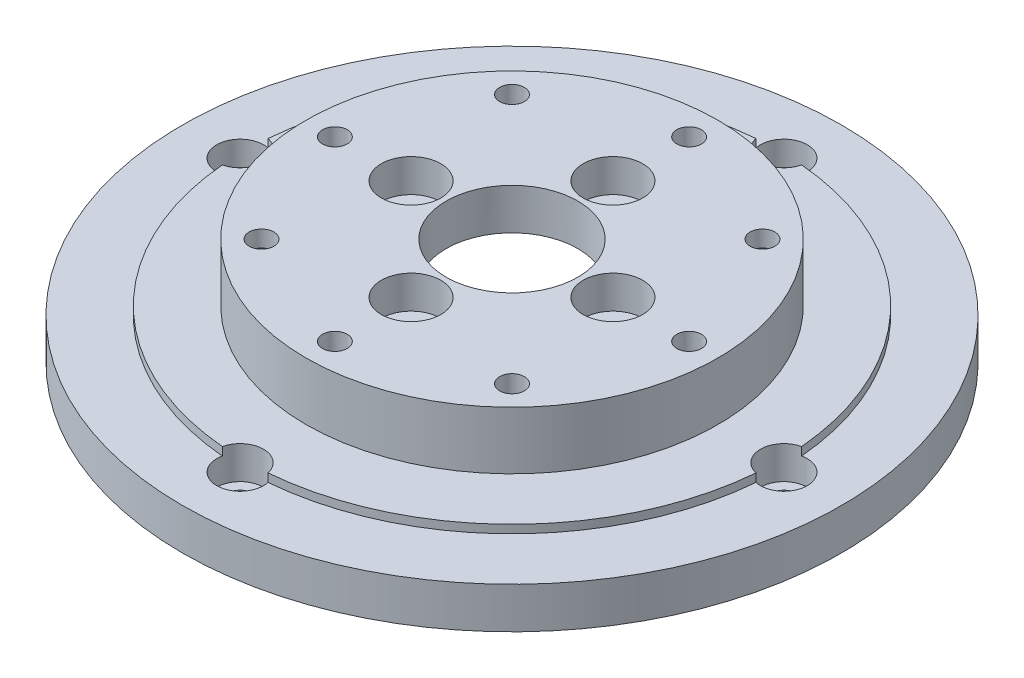
SolidWorks part; units mm, degrees
ref_plane "Front Plane" through (0, 0, 0) normal (0, 0, 1) x (1, 0, 0)
ref_plane "Top Plane" through (0, 0, 0) normal (0, 1, 0) x (1, 0, 0)
ref_plane "Right Plane" through (0, 0, 0) normal (1, 0, 0) x (0, 0, -1)
sketch "Sketch1" plane through (0, 0, 0) normal (0, 1, 0) x (1, 0, 0)
  circle A0 centre (0, 0) radius 40
  circle A2 centre (0, 0) radius 33 construction
  circle A13 centre (0, 0) radius 27.5 construction
  circle A19 centre (0.001, 0.001) radius 27.5 construction
  circle A25 centre (0.002, 0) radius 27.5 construction
  circle A31 centre (0.001, -0.001) radius 27.5 construction
  point P14 (0, 0)
  point P25 (0, 0)
  point P64 (0.001, 0)
  dimension "D1" = 80
  dimension "D3" = 66
  dimension "D6" = 55
  dimension "D10" = 4
extrude "Boss-Extrude1" add sketch "Sketch1" along normal blind 5
sketch "Sketch4" plane through (0, 5, 0) normal (0, 1, 0) x (1, 0, 0)
  circle A0 centre (0, 0) radius 32.5
  dimension "D1" = 65
extrude "Boss-Extrude2" add sketch "Sketch4" along normal blind 1
sketch "Sketch5" plane through (0, 6, 0) normal (0, 1, 0) x (1, 0, 0)
  circle A0 centre (0, 0) radius 25
  dimension "D1" = 50
extrude "Boss-Extrude3" add sketch "Sketch5" along normal blind 7
sketch "Sketch6" plane through (0, 13, 0) normal (0, 1, 0) x (1, 0, 0)
  circle A0 centre (0, 0) radius 12.25 construction
  circle A1 centre (12.25, 0) radius 2
  circle A2 centre (0, -12.25) radius 2
  circle A3 centre (-12.25, 0) radius 2
  circle A4 centre (0, 12.25) radius 2
  circle A5 centre (0, 0) radius 8
  point P14 (0, 0)
  dimension "D1" = 24.5
  dimension "D2" = 4
  dimension "D4" = 16
  dimension "D3" = 4
extrude "Cut-Extrude1" cut sketch "Sketch6" against normal through all
sketch "Sketch7" plane through (0, 0, 0) normal (0, -1, 0) x (1, 0, 0)
  circle A0 centre (0, 0) radius 30
  dimension "D1" = 60
extrude "Cut-Extrude2" cut sketch "Sketch7" against normal blind 4
sketch "Sketch8" plane through (0, 4, 0) normal (0, -1, 0) x (1, 0, 0)
  circle A0 centre (0, 0) radius 24
  dimension "D1" = 48
extrude "Cut-Extrude3" cut sketch "Sketch8" against normal blind 4
sketch "Sketch9" plane through (0, 13, 0) normal (0, 1, 0) x (1, 0, 0)
  circle A0 centre (0, 12.25) radius 3.61
  circle A1 centre (12.25, 0) radius 3.61
  circle A2 centre (0, -12.25) radius 3.61
  circle A3 centre (-12.25, 0) radius 3.61
  point P12 (0, 0)
  dimension "D1" = 7.22
  dimension "D2" = 4
extrude "Cut-Extrude4" cut sketch "Sketch9" against normal blind 4
sketch "Sketch10" plane through (0, 13, 0) normal (0, 1, 0) x (1, 0, 0)
  circle A0 centre (0, 0) radius 33 construction
  circle A1 centre (0, 33) radius 1.57
  circle A2 centre (33, 0) radius 1.57
  circle A3 centre (0, -33) radius 1.57
  circle A4 centre (-33, 0) radius 1.57
  point P14 (0, 0)
  dimension "D1" = 66
  dimension "D2" = 3.14
  dimension "D3" = 4
extrude "Cut-Extrude5" cut sketch "Sketch10" against normal through all
sketch "Sketch11" plane through (0, 6, 0) normal (0, 1, 0) x (1, 0, 0)
  circle A0 centre (0, 33) radius 2.84
  circle A1 centre (33, 0) radius 2.84
  circle A2 centre (0, -33) radius 2.84
  circle A3 centre (-33, 0) radius 2.84
  point P12 (0, 0)
  dimension "D1" = 5.68
  dimension "D2" = 4
extrude "Cut-Extrude6" cut sketch "Sketch11" against normal blind 4
sketch "Sketch12" plane through (0, 13, 0) normal (0, 1, 0) x (1, 0, 0)
  circle A0 centre (0, 0) radius 21.5 construction
  circle A1 centre (0, -21.5) radius 1.5
  circle A2 centre (-15.2028, -15.2028) radius 1.5
  circle A3 centre (-21.5, 0) radius 1.5
  circle A4 centre (-15.2028, 15.2028) radius 1.5
  circle A5 centre (0, 21.5) radius 1.5
  circle A6 centre (15.2028, 15.2028) radius 1.5
  circle A7 centre (21.5, 0) radius 1.5
  circle A8 centre (15.2028, -15.2028) radius 1.5
  point P22 (0, 0)
  dimension "D1" = 43
  dimension "D2" = 3
  dimension "D3" = 8
extrude "Cut-Extrude7" cut sketch "Sketch12" against normal blind 4
sketch "Sketch13" plane through (0, 4, 0) normal (0, -1, 0) x (1, 0, 0)
  line L1 (15.2028, -11.9696) -> (12.4028, -13.5862)
  line L2 (12.4028, -13.5862) -> (12.4028, -16.8194)
  line L3 (12.4028, -16.8194) -> (15.2028, -18.436)
  line L4 (15.2028, -18.436) -> (18.0028, -16.8194)
  line L5 (18.0028, -16.8194) -> (18.0028, -13.5862)
  line L6 (18.0028, -13.5862) -> (15.2028, -11.9696)
  line L7 (-15.2028, 11.9696) -> (-12.4028, 13.5862)
  line L8 (-12.4028, 13.5862) -> (-12.4028, 16.8194)
  line L9 (-12.4028, 16.8194) -> (-15.2028, 18.436)
  line L10 (-15.2028, 18.436) -> (-18.0028, 16.8194)
  line L11 (-18.0028, 16.8194) -> (-18.0028, 13.5862)
  line L12 (-18.0028, 13.5862) -> (-15.2028, 11.9696)
  circle A0 centre (15.2028, -15.2028) radius 1.5 construction
  circle A1 centre (15.2028, -15.2028) radius 1.5 construction
  circle A2 centre (-15.2028, 15.2028) radius 1.5 construction
  circle A3 centre (-15.2028, 15.2028) radius 1.5 construction
  circle A4 centre (15.2028, -15.2028) radius 2.8 construction
  circle A5 centre (-15.2028, 15.2028) radius 2.8 construction
  dimension "D1" = 5.6
  dimension "D2" = 5.6
extrude "Cut-Extrude9" cut sketch "Sketch13" against normal blind 7
